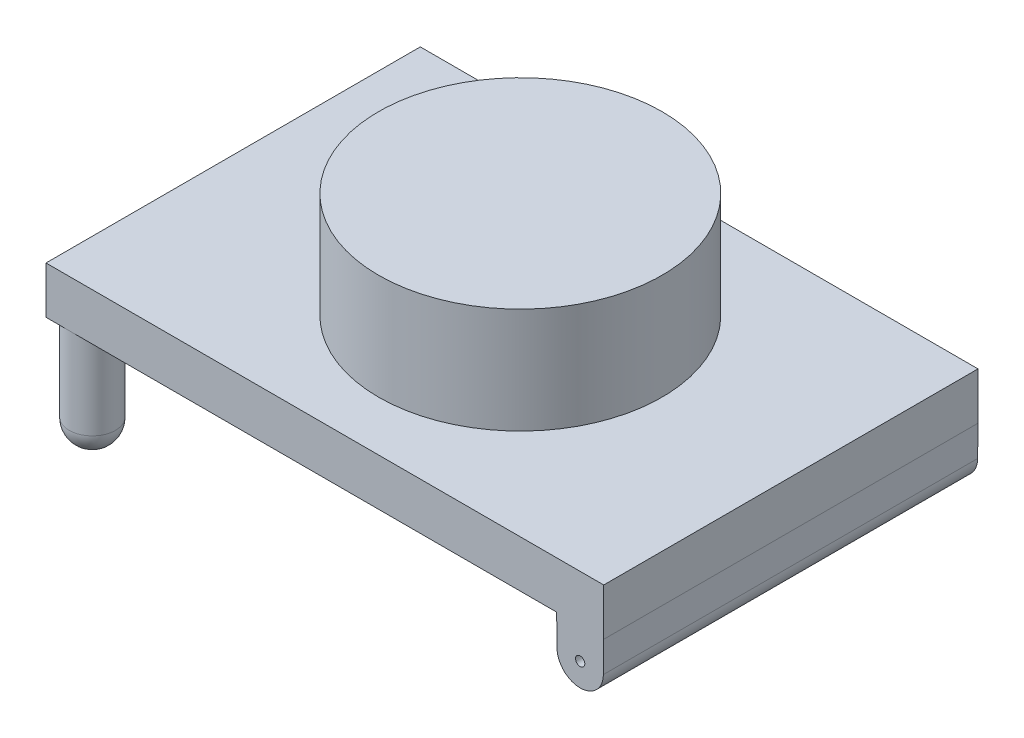
SolidWorks part; units mm, degrees
ref_plane "Front Plane" through (0, 0, 0) normal (0, 0, 1) x (1, 0, 0)
ref_plane "Top Plane" through (0, 0, 0) normal (0, 1, 0) x (1, 0, 0)
ref_plane "Right Plane" through (0, 0, 0) normal (1, 0, 0) x (0, 0, -1)
sketch "Sketch1" plane through (0, 0, 0) normal (0, 1, 0) x (1, 0, 0)
  line L1 (150.5, -101) -> (-150.5, -101)
  line L2 (150.5, -101) -> (150.5, 101)
  line L3 (150.5, 101) -> (-150.5, 101)
  line L4 (-150.5, -101) -> (-150.5, 101)
  line L5 (150.5, -101) -> (-150.5, 101) construction
  line L6 (150.5, 101) -> (-150.5, -101) construction
  point P0 (0, 0)
  dimension "D1" = 301
  dimension "D2" = 202
extrude "Boss-Extrude1" add sketch "Sketch1" along normal blind 60
sketch "Sketch2" plane through (0, 0, 101) normal (0, 0, 1) x (1, 0, 0)
  line L0 (-150.5, 60) -> (150.5, 60) construction
  line L1 (150.5, 60) -> (150.5, 0) construction
  circle A0 centre (137.8, 18) radius 2.5
  dimension "D1" = 5
  dimension "D2" = 42
  dimension "D3" = 12.7
sketch "Sketch4" plane through (0, 0, 101) normal (0, 0, 1) x (1, 0, 0)
  line L0 (137.8, 18) -> (137.8, 60) construction
  line L1 (125.1, 60) -> (150.5, 60)
  line L2 (125.1, 60) -> (125.1, 34.6)
  line L3 (125.1, 34.6) -> (150.5, 34.6)
  line L4 (150.5, 60) -> (150.5, 34.6)
  line L5 (-150.5, 60) -> (150.5, 60) construction
  line L6 (125.3, 18) -> (125.1, 34.6)
  line L7 (150.3, 18) -> (150.5, 34.6)
  line L8 (-150.5, 60) -> (125.1, 60)
  line L9 (-150.5, 60) -> (-150.5, 34.6)
  line L10 (-150.5, 34.6) -> (125.1, 34.6)
  line L11 (125.1, 60) -> (125.1, 34.6)
  circle A0 centre (137.8, 18) radius 12.5
  line M12 (-150.5, 0) -> (150.5, 0)
  line M13 (150.5, 0) -> (150.5, 60)
  line M15 (-150.5, 60) -> (-150.5, 0)
  dimension "D1" = 25
  dimension "D2" = 25.4
  dimension "D3" = 25.4
  dimension "D4" = 25.4
extrude "Cut-Extrude1" cut sketch "Sketch4" against normal through all contours A0 L6 L10 L7 M15 M12 M13 region at (-9.3803, 17.0289, 101)
sketch "Sketch5" plane through (0, 34.6, 0) normal (0, -1, 0) x (1, 0, 0)
  line L0 (-138, 88.5) -> (-138, -88.5) construction
  line L1 (-150.5, -101) -> (-150.5, 101) construction
  line L2 (-150.5, -101) -> (125.1, -101) construction
  line L3 (-150.5, 101) -> (125.1, 101) construction
  circle A0 centre (-138, 88.5) radius 12.5
  circle A1 centre (-138, -88.5) radius 12.5
  dimension "D1" = 25
extrude "Boss-Extrude2" add sketch "Sketch5" along normal blind 59.1
fillet "Fillet1" radius 12.5 2 edges at (-138, -24.5, -101) (-138, -24.5, 76)
extrude "Cut-Extrude2" cut sketch "Sketch2" against normal through all contours A0
sketch "Sketch6" plane through (0, 60, 0) normal (0, 1, 0) x (1, 0, 0)
  line L0 (2, -74) -> (2, -101) construction
  line L1 (-150.5, -101) -> (150.5, -101) construction
  line L2 (2, 79) -> (2, 101) construction
  line L3 (150.5, 101) -> (-150.5, 101) construction
  line L4 (-74.5, 2.5) -> (-150.5, 2.5) construction
  line L5 (-150.5, 101) -> (-150.5, -101) construction
  circle A0 centre (2, 2.5) radius 76.5
  dimension "D1" = 22
  dimension "D2" = 27
  dimension "D3" = 76
extrude "Boss-Extrude3" add sketch "Sketch6" along normal blind 57
sketch "Sketch7" plane through (0, 117, 0) normal (0, 1, 0) x (1, 0, 0)
  line L1 (-150.5, -101) -> (150.5, -101) construction
  line L2 (150.5, 101) -> (-150.5, 101) construction
  line L3 (-150.5, 101) -> (-150.5, -101) construction
  circle A0 centre (-35.5, -34) radius 1.5
  circle A1 centre (-24.5, 34) radius 1.5
  point P12 (139.8314, 104.0028)
  point P13 (-164.3295, 79.4055)
  dimension "D5" = 3
  dimension "D6" = 3
  dimension "D1" = 115
  dimension "D2" = 126
  dimension "D3" = 67
  dimension "D4" = 67
